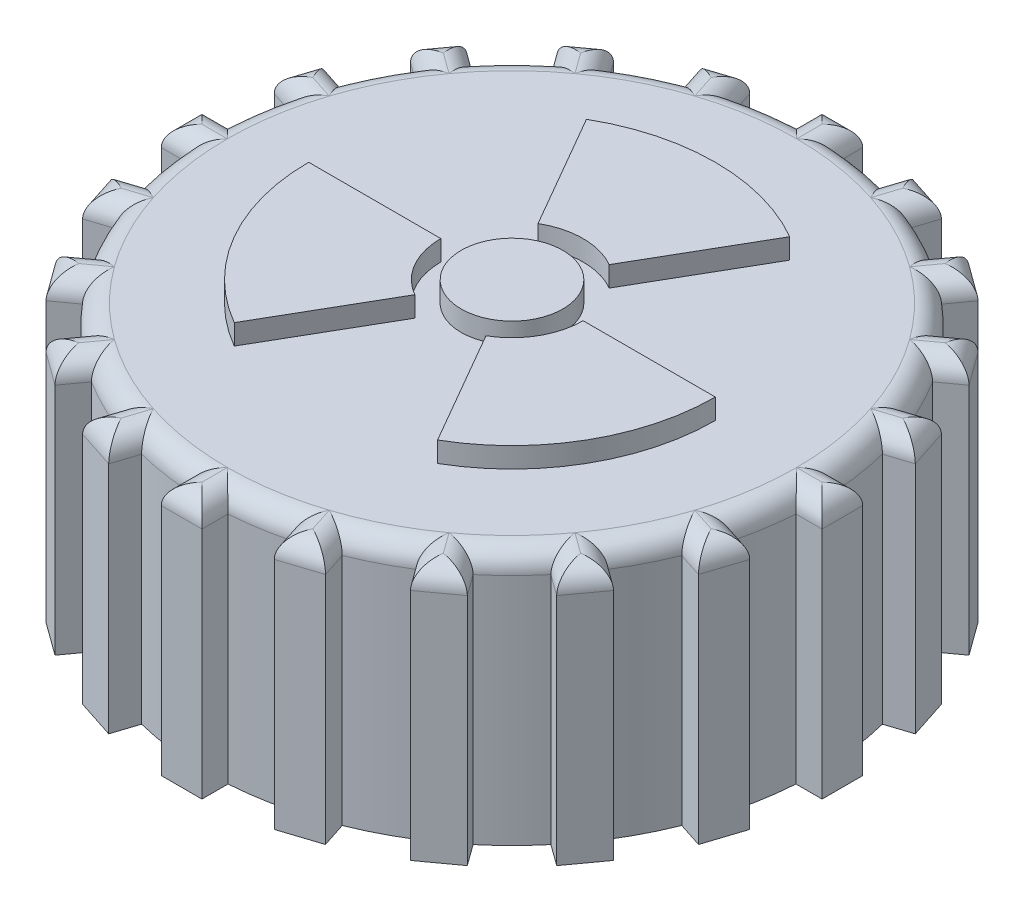
SolidWorks part; units mm, degrees
ref_plane "Front Plane" through (0, 0, 0) normal (0, 0, 1) x (1, 0, 0)
ref_plane "Top Plane" through (0, 0, 0) normal (0, 1, 0) x (1, 0, 0)
ref_plane "Right Plane" through (0, 0, 0) normal (1, 0, 0) x (0, 0, -1)
sketch "Sketch1" plane through (0, 0, 0) normal (0, 1, 0) x (1, 0, 0)
  circle A0 centre (0, 0) radius 25
  circle A1 centre (0, 0) radius 30
extrude "Boss-Extrude1" add sketch "Sketch1" against normal blind 20
sketch "Sketch2" plane through (0, 0, 0) normal (0, 1, 0) x (1, 0, 0)
  circle A0 centre (0, 0) radius 30
extrude "Boss-Extrude2" add sketch "Sketch2" along normal blind 5
sketch "Sketch3" plane through (0, 5, 0) normal (0, 1, 0) x (1, 0, 0)
  line L0 (0, 0) -> (0, 30) construction
  line L1 (11.152, 27.8502) -> (11.9452, 30.2913)
  line L3 (-2, 29.9333) -> (-2, 32.5)
  line L4 (-2, 32.5) -> (2, 32.5)
  line L5 (2, 29.9333) -> (2, 32.5)
  line L6 (-2, 27.5) -> (2, 32.5) construction
  line L7 (-2, 32.5) -> (2, 27.5) construction
  line L8 (8.1409, 31.5274) -> (11.9452, 30.2913)
  line L9 (7.3478, 29.0863) -> (8.1409, 31.5274)
  line L10 (19.2124, 23.0409) -> (20.7211, 25.1175)
  line L11 (17.485, 27.4686) -> (20.7211, 25.1175)
  line L12 (15.9763, 25.3921) -> (17.485, 27.4686)
  line L13 (25.3921, 15.9763) -> (27.4686, 17.485)
  line L14 (25.1175, 20.7211) -> (27.4686, 17.485)
  line L15 (23.0409, 19.2124) -> (25.1175, 20.7211)
  line L16 (29.0863, 7.3478) -> (31.5274, 8.1409)
  line L17 (30.2913, 11.9452) -> (31.5274, 8.1409)
  line L18 (27.8502, 11.152) -> (30.2913, 11.9452)
  line L19 (29.9333, -2) -> (32.5, -2)
  line L20 (32.5, 2) -> (32.5, -2)
  line L21 (29.9333, 2) -> (32.5, 2)
  line L22 (27.8502, -11.152) -> (30.2913, -11.9452)
  line L23 (31.5274, -8.1409) -> (30.2913, -11.9452)
  line L24 (29.0863, -7.3478) -> (31.5274, -8.1409)
  line L25 (23.0409, -19.2124) -> (25.1175, -20.7211)
  line L26 (27.4686, -17.485) -> (25.1175, -20.7211)
  line L27 (25.3921, -15.9763) -> (27.4686, -17.485)
  line L28 (15.9763, -25.3921) -> (17.485, -27.4686)
  line L29 (20.7211, -25.1175) -> (17.485, -27.4686)
  line L30 (19.2124, -23.0409) -> (20.7211, -25.1175)
  line L31 (7.3478, -29.0863) -> (8.1409, -31.5274)
  line L32 (11.9452, -30.2913) -> (8.1409, -31.5274)
  line L33 (11.152, -27.8502) -> (11.9452, -30.2913)
  line L34 (-2, -29.9333) -> (-2, -32.5)
  line L35 (2, -32.5) -> (-2, -32.5)
  line L36 (2, -29.9333) -> (2, -32.5)
  line L37 (-11.152, -27.8502) -> (-11.9452, -30.2913)
  line L38 (-8.1409, -31.5274) -> (-11.9452, -30.2913)
  line L39 (-7.3478, -29.0863) -> (-8.1409, -31.5274)
  line L40 (-19.2124, -23.0409) -> (-20.7211, -25.1175)
  line L41 (-17.485, -27.4686) -> (-20.7211, -25.1175)
  line L42 (-15.9763, -25.3921) -> (-17.485, -27.4686)
  line L43 (-25.3921, -15.9763) -> (-27.4686, -17.485)
  line L44 (-25.1175, -20.7211) -> (-27.4686, -17.485)
  line L45 (-23.0409, -19.2124) -> (-25.1175, -20.7211)
  line L46 (-29.0863, -7.3478) -> (-31.5274, -8.1409)
  line L47 (-30.2913, -11.9452) -> (-31.5274, -8.1409)
  line L48 (-27.8502, -11.152) -> (-30.2913, -11.9452)
  line L49 (-29.9333, 2) -> (-32.5, 2)
  line L50 (-32.5, -2) -> (-32.5, 2)
  line L51 (-29.9333, -2) -> (-32.5, -2)
  line L52 (-27.8502, 11.152) -> (-30.2913, 11.9452)
  line L53 (-31.5274, 8.1409) -> (-30.2913, 11.9452)
  line L54 (-29.0863, 7.3478) -> (-31.5274, 8.1409)
  line L55 (-23.0409, 19.2124) -> (-25.1175, 20.7211)
  line L56 (-27.4686, 17.485) -> (-25.1175, 20.7211)
  line L57 (-25.3921, 15.9763) -> (-27.4686, 17.485)
  line L58 (-15.9763, 25.3921) -> (-17.485, 27.4686)
  line L59 (-20.7211, 25.1175) -> (-17.485, 27.4686)
  line L60 (-19.2124, 23.0409) -> (-20.7211, 25.1175)
  line L61 (-7.3478, 29.0863) -> (-8.1409, 31.5274)
  line L62 (-11.9452, 30.2913) -> (-8.1409, 31.5274)
  line L63 (-11.152, 27.8502) -> (-11.9452, 30.2913)
  circle A0 centre (0, 0) radius 30 construction
  arc A1 (2, 29.9333) -> (-2, 29.9333) centre (0, 0) ccw
  arc A2 (11.152, 27.8502) -> (7.3478, 29.0863) centre (0, 0) ccw
  arc A3 (19.2124, 23.0409) -> (15.9763, 25.3921) centre (0, 0) ccw
  arc A4 (25.3921, 15.9763) -> (23.0409, 19.2124) centre (0, 0) ccw
  arc A5 (29.0863, 7.3478) -> (27.8502, 11.152) centre (0, 0) ccw
  arc A6 (29.9333, -2) -> (29.9333, 2) centre (0, 0) ccw
  arc A7 (27.8502, -11.152) -> (29.0863, -7.3478) centre (0, 0) ccw
  arc A8 (23.0409, -19.2124) -> (25.3921, -15.9763) centre (0, 0) ccw
  arc A9 (15.9763, -25.3921) -> (19.2124, -23.0409) centre (0, 0) ccw
  arc A10 (7.3478, -29.0863) -> (11.152, -27.8502) centre (0, 0) ccw
  arc A11 (-2, -29.9333) -> (2, -29.9333) centre (0, 0) ccw
  arc A12 (-11.152, -27.8502) -> (-7.3478, -29.0863) centre (0, 0) ccw
  arc A13 (-19.2124, -23.0409) -> (-15.9763, -25.3921) centre (0, 0) ccw
  arc A14 (-25.3921, -15.9763) -> (-23.0409, -19.2124) centre (0, 0) ccw
  arc A15 (-29.0863, -7.3478) -> (-27.8502, -11.152) centre (0, 0) ccw
  arc A16 (-29.9333, 2) -> (-29.9333, -2) centre (0, 0) ccw
  arc A17 (-27.8502, 11.152) -> (-29.0863, 7.3478) centre (0, 0) ccw
  arc A18 (-23.0409, 19.2124) -> (-25.3921, 15.9763) centre (0, 0) ccw
  arc A19 (-15.9763, 25.3921) -> (-19.2124, 23.0409) centre (0, 0) ccw
  arc A20 (-7.3478, 29.0863) -> (-11.152, 27.8502) centre (0, 0) ccw
  point P91 (0, 0)
  dimension "D1" = 20
extrude "Boss-Extrude3" add sketch "Sketch3" against normal blind 25
fillet "Fillet1" radius 2 80 edges at (21.2132, 5, 21.2132) (19.103, 5, 26.2931) (19.9667, 5, 24.0792) (16.7306, 5, 26.4304) (13.6197, 5, 26.7302) (10.0431, 5, 30.9093) (11.5486, 5, 29.0707) (7.7444, 5, 30.3068) (4.693, 5, 29.6307) (0, 5, 32.5) (2, 5, 31.2166) (-2, 5, 31.2166) (-4.693, 5, 29.6307) (-10.0431, 5, 30.9093) (-7.7444, 5, 30.3068) (-11.5486, 5, 29.0707) (-4.693, 5, -29.6307) (-13.6197, 5, 26.7302) (-19.103, 5, 26.2931) (-16.7306, 5, 26.4304) (-19.9667, 5, 24.0792) (-21.2132, 5, 21.2132) (-26.2931, 5, 19.103) (-24.0792, 5, 19.9667) (-26.4304, 5, 16.7306) (-26.7302, 5, 13.6197) (-30.9093, 5, 10.0431) (-29.0707, 5, 11.5486) (-30.3068, 5, 7.7444) (2, 5, -31.2166) (0, 5, -32.5) (-29.6307, 5, 4.693) (-2, 5, -31.2166) (-32.5, 5, 0) (-31.2166, 5, 2) (-31.2166, 5, -2) (-29.6307, 5, -4.693) (-30.9093, 5, -10.0431) (-30.3068, 5, -7.7444) (-29.0707, 5, -11.5486) (-26.7302, 5, -13.6197) (-26.2931, 5, -19.103) (-26.4304, 5, -16.7306) (-24.0792, 5, -19.9667) (-21.2132, 5, -21.2132) (-19.103, 5, -26.2931) (-19.9667, 5, -24.0792) (-16.7306, 5, -26.4304) (-13.6197, 5, -26.7302) (-10.0431, 5, -30.9093) (-11.5486, 5, -29.0707) (-7.7444, 5, -30.3068) (4.693, 5, -29.6307) (10.0431, 5, -30.9093) (7.7444, 5, -30.3068) (11.5486, 5, -29.0707) (13.6197, 5, -26.7302) (19.103, 5, -26.2931) (16.7306, 5, -26.4304) (19.9667, 5, -24.0792) (21.2132, 5, -21.2132) (26.2931, 5, -19.103) (24.0792, 5, -19.9667) (26.4304, 5, -16.7306) (26.7302, 5, -13.6197) (30.9093, 5, -10.0431) (29.0707, 5, -11.5486) (30.3068, 5, -7.7444) (29.6307, 5, -4.693) (32.5, 5, 0) (31.2166, 5, -2) (31.2166, 5, 2) (29.6307, 5, 4.693) (30.9093, 5, 10.0431) (30.3068, 5, 7.7444) (29.0707, 5, 11.5486) (26.7302, 5, 13.6197) (26.2931, 5, 19.103) (26.4304, 5, 16.7306) (24.0792, 5, 19.9667)
sketch "Sketch4" plane through (0, 5, 0) normal (0, 1, 0) x (1, 0, 0)
  line L0 (0, 0) -> (0, 20) construction
  line L1 (0, 0) -> (-10, 17.3205) construction
  line L2 (-10, 17.3205) -> (-3.5, 6.0622)
  line L3 (10, 17.3205) -> (3.5, 6.0622)
  line L4 (20, 0) -> (7, 0)
  line L5 (10, -17.3205) -> (3.5, -6.0622)
  line L6 (-10, -17.3205) -> (-3.5, -6.0622)
  line L7 (-20, 0) -> (-7, 0)
  circle A0 centre (0, 0) radius 5
  arc A1 (10, 17.3205) -> (-10, 17.3205) centre (0, 0) ccw
  arc A2 (3.5, 6.0622) -> (-3.5, 6.0622) centre (0, 0) ccw
  arc A3 (10, -17.3205) -> (20, 0) centre (0, 0) ccw
  arc A4 (3.5, -6.0622) -> (7, 0) centre (0, 0) ccw
  arc A5 (-20, 0) -> (-10, -17.3205) centre (0, 0) ccw
  arc A6 (-7, 0) -> (-3.5, -6.0622) centre (0, 0) ccw
  point P19 (0, 0)
  dimension "D1" = 30
  dimension "D2" = 3
extrude "Boss-Extrude4" add sketch "Sketch4" along normal blind 2 separate body
